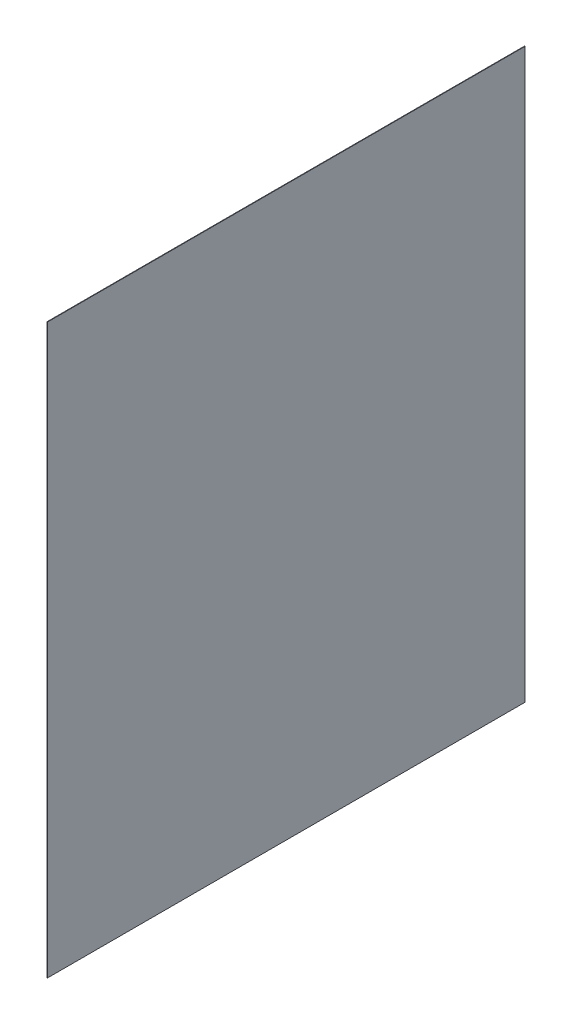
SolidWorks part; units mm, degrees
ref_plane "Front Plane" through (0, 0, 0) normal (0, 0, 1) x (1, 0, 0)
ref_plane "Top Plane" through (0, 0, 0) normal (0, 1, 0) x (1, 0, 0)
ref_plane "Right Plane" through (0, 0, 0) normal (1, 0, 0) x (0, 0, -1)
sketch "Sketch1" plane through (0, 0, 0) normal (1, 0, 0) x (0, 0, -1)
  line L1 (0, 0) -> (661.7, 0)
  line L2 (0, 0) -> (0, 787.05)
  line L3 (0, 787.05) -> (661.7, 787.05)
  line L4 (661.7, 0) -> (661.7, 787.05)
  dimension "D1" = 787.05
  dimension "D2" = 661.7
base flange "Base-Flange1" sketch "Sketch1" thickness 0.7 reverse thickness direction no parameters "D1"=0.7
sketch "Bend-Lines1" [suppressed] plane through (0, 0, 0) normal (0, 1, 0) x (1, 0, 0)
sketch "Bounding-Box1" [suppressed] plane through (0, 0, 0) normal (0, 1, 0) x (1, 0, 0)
sheet metal parameters "Sheet-Metal1" thickness 0.7 parameters "D1"=0.7
flat pattern "Flat-Pattern1" [suppressed]
sketch "Bend-Lines2" plane through (0, 0, 0) normal (0, 1, 0) x (1, 0, 0)
sketch3d "Bounding-Box2" [suppressed]
  line L0 (0, 787.05, 0) -> (0, 0, 0) construction
  line L1 (661.7, 787.05, 0) -> (661.7, 0, 0) construction
  line L2 (0, 787.05, 0) -> (661.7, 787.05, 0) construction
  line L3 (0, 0, 0) -> (661.7, 0, 0) construction
